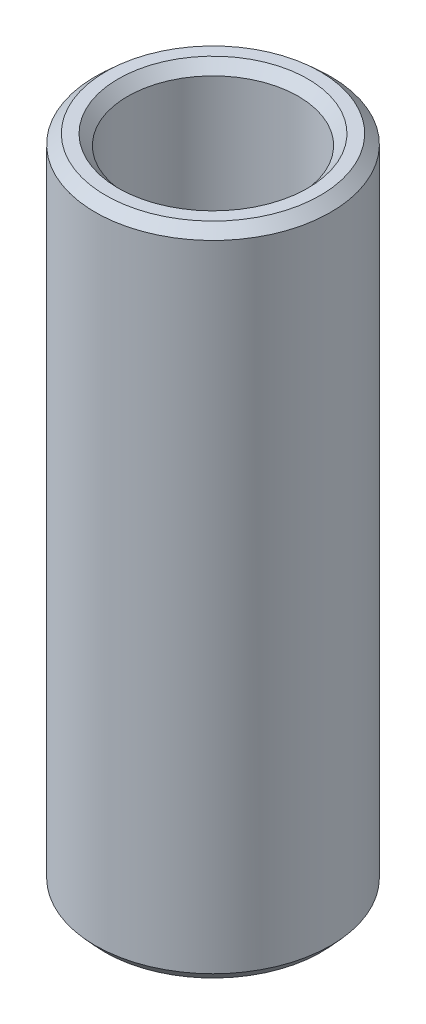
SolidWorks part; units mm, degrees
ref_plane "Front Plane" through (0, 0, 0) normal (0, 0, 1) x (1, 0, 0)
ref_plane "Top Plane" through (0, 0, 0) normal (0, 1, 0) x (1, 0, 0)
ref_plane "Right Plane" through (0, 0, 0) normal (1, 0, 0) x (0, 0, -1)
sketch "Sketch1" plane through (0, 0, 0) normal (0, 1, 0) x (1, 0, 0)
  circle A0 centre (0, 0) radius 37.5
  dimension "SLEEVE_OD" = 75
extrude "Boss-Extrude1" add sketch "Sketch1" along normal blind 208.7261
sketch "Sketch2" plane through (0, 0, 0) normal (0, 1, 0) x (1, 0, 0)
  circle A0 centre (0, 0) radius 27.1932
  dimension "BORE_D" = 54.3864
extrude "Cut-Extrude1" cut sketch "Sketch2" along normal through all
chamfer "Chamfer1" distance 3.0076 angle 47.74 4 edges at (0, 208.7261, 27.1932) (0, 0, 27.1932) (0, 0, 37.5) (0, 208.7261, 37.5) first distance on face at (0, 208.7261, 27.1932) first distance on face at (0, 0, 27.1932) first distance on face at (0, 208.7261, 37.5)
